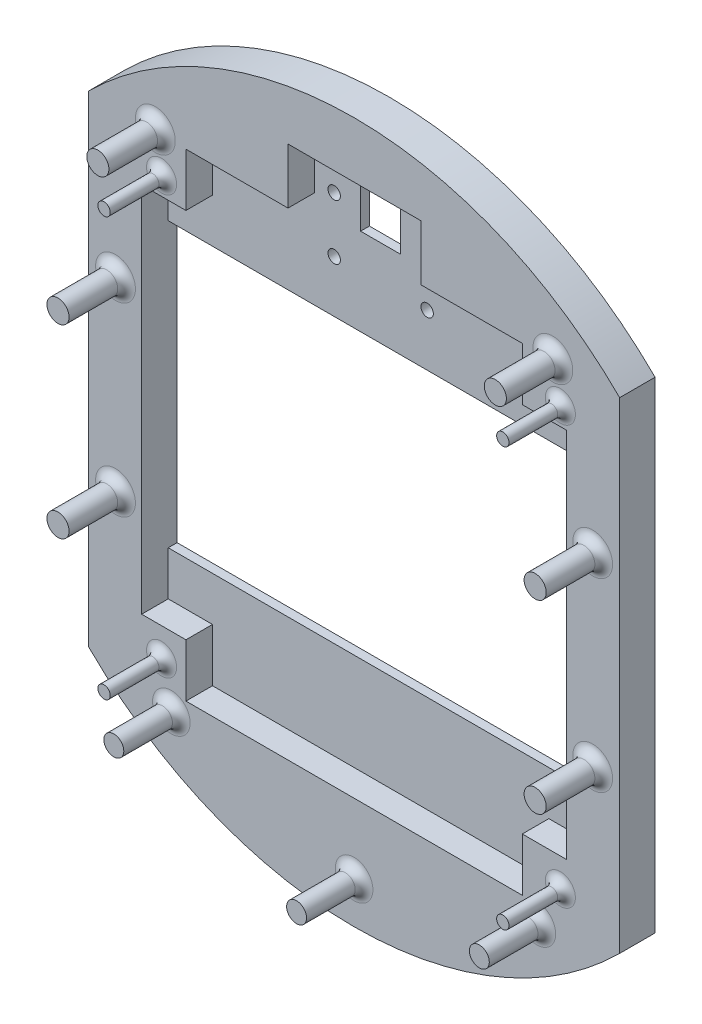
SolidWorks part; units mm, degrees
material "ABS"
ref_plane "Plano frontal" through (0, 0, 0) normal (0, 0, 1) x (1, 0, 0)
ref_plane "Plano superior" through (0, 0, 0) normal (0, 1, 0) x (1, 0, 0)
ref_plane "Plano direito" through (0, 0, 0) normal (1, 0, 0) x (0, 0, -1)
sketch "Esboço1" plane through (0, 0, 0) normal (0, 0, 1) x (1, 0, 0)
  line L0 (0, 0) -> (0, -108.75)
  line L1 (120, -108.75) -> (120, 0)
  line L2 (60, -11.4098) -> (60, -97.3402) construction
  line L3 (120, -54.375) -> (-37.4329, -54.375) construction
  line L4 (12, -86.375) -> (108, -86.375)
  line L5 (12, -86.375) -> (12, -22.375)
  line L6 (12, -22.375) -> (108, -22.375)
  line L7 (108, -86.375) -> (108, -22.375)
  line L8 (12, -86.375) -> (108, -22.375) construction
  line L9 (12, -22.375) -> (108, -86.375) construction
  arc A4 (0, 0) -> (120, 0) centre (60, -60.208) cw
  arc A5 (0, -108.75) -> (120, -108.75) centre (60, -48.542) ccw
  point P9 (60, -54.375)
  point P17 (60, 24.792)
  dimension "D1" = 108.75
  dimension "D5" = 85
  dimension "D2" = 64
  dimension "D3" = 96
extrude "Ressalto-extrusão1" add sketch "Esboço1" along normal blind 8
sketch "Esboço2" plane through (0, 0, 8) normal (0, 0, 1) x (1, 0, 0)
  line L0 (12, -54.375) -> (108, -54.375) construction
  line L1 (12, -22.375) -> (12, -86.375) construction
  line L2 (108, -86.375) -> (108, -22.375) construction
  line L3 (108, -22.375) -> (12, -22.375) construction
  line L4 (12, -96.375) -> (108, -96.375)
  line L5 (12, -96.375) -> (12, -12.375)
  line L6 (12, -12.375) -> (108, -12.375)
  line L7 (108, -96.375) -> (108, -12.375)
  line L8 (12, -96.375) -> (108, -12.375) construction
  line L9 (12, -12.375) -> (108, -96.375) construction
  point P6 (60, -54.375)
  dimension "D1" = 10
extrude "Corte-extrusão1" cut sketch "Esboço2" against normal blind 6
sketch "Esboço3" plane through (0, 0, 8) normal (0, 0, 1) x (1, 0, 0)
  line L0 (-24.8022, -47.1436) -> (153.0643, -47.1436) construction
  line L1 (113.9062, -94.6477) -> (113.9062, -101.6218) construction
  line L2 (6.0938, 0) -> (113.9062, 0) construction
  line L3 (60, 24.792) -> (60, -133.542) construction
  line L5 (0, 0) -> (0, -108.75) construction
  line L6 (0, -12.5) -> (6.0938, -12.5) construction
  line L7 (6.0938, -12.5) -> (6.0938, -102.188) construction
  line L8 (35.13, -12.375) -> (35.13, -106.875) construction
  line L9 (108, -12.375) -> (12, -12.375) construction
  line L10 (60, -133.542) -> (60, -106.875)
  arc A0 (6.0938, -102.188) -> (113.9062, -102.188) centre (60, -47.1436) ccw
  circle A1 centre (18.7084, -112.188) radius 2.25
  circle A2 centre (60, -124.1876) radius 2.25
  circle A3 centre (101.2916, -112.188) radius 2.25
  circle A4 centre (104.9062, 0) radius 2.5
  circle A6 centre (15.0938, 0) radius 2.5
  arc A7 (120, 0) -> (0, 0) centre (60, -60.208) ccw construction
  arc A8 (0, -108.75) -> (120, -108.75) centre (60, -48.542) ccw construction
  circle A9 centre (6.0938, -75.315) radius 2.5
  circle A10 centre (6.0938, -33.44) radius 2.5
  circle A11 centre (113.9062, -75.315) radius 2.5
  circle A12 centre (113.9062, -33.44) radius 2.5
  point P39 (60, -12.375)
  dimension "D1" = 4.5
  dimension "D2" = 5
  dimension "D7" = 77.044
  dimension "D3" = 41.875
  dimension "D4" = 20.94
  dimension "D5" = 10
  dimension "D6" = 89.688
  dimension "D8" = 41.2916
  dimension "D9" = 26.667
  dimension "D10" = 37.167
  dimension "D11" = 9.3545
  dimension "D12" = 107.8125
  dimension "D13" = 9
  dimension "D14" = 9
extrude "Ressalto-extrusão2" add sketch "Esboço3" along normal blind 13 contours A9 | A1 | A2 | A3 | A11 | A12 | A4 | A6 | A10
fillet "Filete1" radius 2 9 edges at (12.5938, 0, 8) (3.5937, -33.44, 8) (3.5937, -75.315, 8) (16.4584, -112.188, 8) (57.75, -124.1876, 8) (99.0416, -112.188, 8) (111.4062, -75.315, 8) (111.4063, -33.44, 8) (102.4062, 0, 8)
sketch "Esboço5" plane through (0, 0, 8) normal (0, 0, 1) x (1, 0, 0)
  line L0 (47.0593, -12.375) -> (47.0593, 1.21)
  line L1 (108, -12.375) -> (12, -12.375) construction
  line L2 (47.0593, 1.21) -> (73.076, 1.21)
  line L3 (73.076, 1.21) -> (73.076, -25.3836)
  line L4 (73.076, -25.3836) -> (47.0593, -25.3836)
  line L5 (47.0593, -25.3836) -> (47.0593, -12.375)
extrude "Corte-extrusão3" cut sketch "Esboço5" against normal blind 5
sketch "Esboço6" plane through (0, 0, 8) normal (0, 0, 1) x (1, 0, 0)
  line L0 (60, 24.792) -> (60, -141.3459) construction
  line L1 (0, -54.375) -> (135.5539, -54.375) construction
  line L2 (0, 0) -> (0, -108.75) construction
  circle A0 centre (16.5, -8.315) radius 1.4
  arc A1 (120, 0) -> (0, 0) centre (60, -60.208) ccw construction
  circle A5 centre (106.6, -102.835) radius 1.4
  circle A6 centre (16.5, -102.835) radius 1.4
  circle A7 centre (106.6, -8.315) radius 1.4
  dimension "D1" = 2.8
extrude "Ressalto-extrusão3" add sketch "Esboço6" along normal up to surface (13 mm away) up to face at (111.4062, -75.315, 21)
fillet "Filete2" radius 2 4 edges at (105.2, -8.315, 8) (15.1, -102.835, 8) (105.2, -102.835, 8) (15.1, -8.315, 8)
sketch "Esboço8" plane through (0, 0, 8) normal (0, 0, 1) x (1, 0, 0)
  line L0 (45.0677, 1.21) -> (45.0677, 12.1682)
  line L1 (45.0677, 12.1682) -> (75.0677, 12.1682)
  line L2 (75.0677, 12.1682) -> (75.0677, -15.935)
  line L3 (75.0677, -15.935) -> (45.0677, -15.935)
  line L4 (45.0677, -15.935) -> (45.0677, 1.21)
  line L5 (73.076, 1.21) -> (47.0593, 1.21) construction
  point P8 (60.0677, -15.935)
  point P11 (60.0677, 1.21)
  dimension "D1" = 30
extrude "Corte-extrusão5" cut sketch "Esboço8" against normal up to surface (6 mm away) up to face at (60, -17.375, 2)
sketch "Esboço9" plane through (0, 0, 2) normal (0, 0, 1) x (1, 0, 0)
  line L1 (55.4685, 6.3063) -> (64.4685, 6.3063)
  line L2 (55.4685, 6.3063) -> (55.4685, -2.6937)
  line L3 (55.4685, -2.6937) -> (64.4685, -2.6937)
  line L4 (64.4685, 6.3063) -> (64.4685, -2.6937)
  line L5 (55.4685, 6.3063) -> (64.4685, -2.6937) construction
  line L6 (55.4685, -2.6937) -> (64.4685, 6.3063) construction
  circle A0 centre (49.5, -10.635) radius 1.4
  circle A1 centre (49.5, 1.865) radius 1.4
  circle A2 centre (70.5, 1.865) radius 1.4
  circle A3 centre (70.5, -10.635) radius 1.4
  point P12 (59.9685, 1.8063)
  dimension "D3" = 2.8
  dimension "D1" = 9
  dimension "D2" = 9
extrude "Corte-extrusão6" cut sketch "Esboço9" against normal through all
sketch "Esboço10" plane through (0, 0, 8) normal (0, 0, 1) x (1, 0, 0)
  line L6 (60, 24.792) -> (60, -137.3046) construction
  line L7 (0, -54.375) -> (133.7853, -54.375) construction
  line L8 (0, 0) -> (0, -108.75) construction
  line L21 (98, -0.375) -> (98, -12.375)
  line L22 (22, -0.375) -> (98, -0.375)
  line L24 (22, -0.375) -> (22, -12.375)
  line L25 (108, -12.375) -> (75.0677, -12.375) construction
  line L26 (0, 0) -> (0, -108.75)
  line L27 (120, -108.75) -> (120, 0)
  line L28 (0, 0) -> (0, -108.75)
  line L29 (120, -108.75) -> (120, 0)
  line L30 (45.0677, -12.375) -> (12, -12.375) construction
  line L31 (22, -12.375) -> (98, -12.375)
  line L32 (22, -108.375) -> (22, -96.375)
  line L33 (22, -108.375) -> (98, -108.375)
  line L34 (98, -108.375) -> (98, -96.375)
  line L35 (22, -96.375) -> (98, -96.375)
  arc A0 (120, 0) -> (0, 0) centre (60, -60.208) ccw construction
  arc A3 (120, 0) -> (0, 0) centre (60, -60.208) ccw
  arc A4 (0, -108.75) -> (120, -108.75) centre (60, -48.542) ccw
  arc A5 (120, 0) -> (0, 0) centre (60, -60.208) ccw
  arc A6 (0, -108.75) -> (120, -108.75) centre (60, -48.542) ccw
  point P1 (0, 0)
  point P5 (0, 0)
  point P17 (22.0009, 0)
  point P22 (22.0009, 0)
  point P23 (22.5785, -9.715)
  dimension "D1" = 76
  dimension "D3" = 12
  dimension "D5" = 38
  dimension "D6" = 12
  dimension "D4" = 0
extrude "Corte-extrusão8" cut sketch "Esboço10" against normal blind 6 flip side to cut
